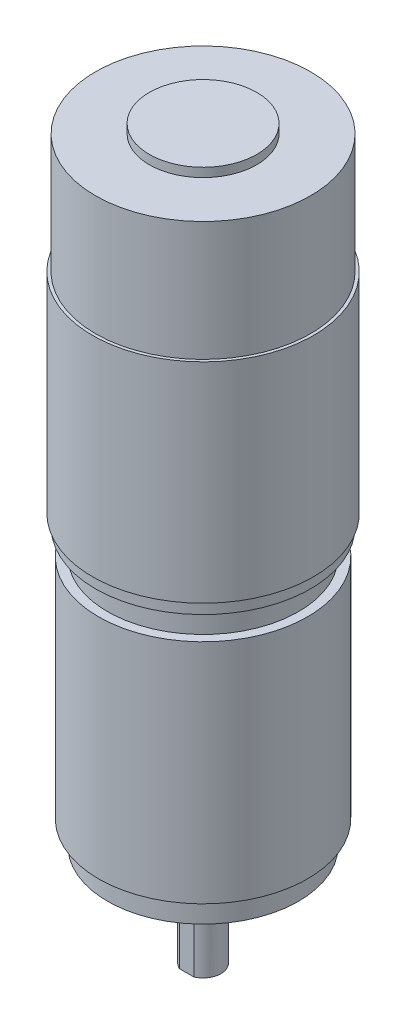
SolidWorks part; units mm, degrees
ref_plane "Спереди" through (0, 0, 0) normal (0, 0, 1) x (1, 0, 0)
ref_plane "Сверху" through (0, 0, 0) normal (0, 1, 0) x (1, 0, 0)
ref_plane "Справа" through (0, 0, 0) normal (1, 0, 0) x (0, 0, -1)
sketch "Эскиз1" plane through (0, 0, 0) normal (0, 0, 1) x (1, 0, 0)
  line L0 (0, -180.9093) -> (0, 224.9568) construction
  line L1 (0, 0) -> (-9, 0)
  line L2 (-9, 0) -> (-9, -1.5)
  line L3 (-9, -1.5) -> (-18, -1.5)
  line L4 (-18, -1.5) -> (-18, -21.5)
  line L5 (-18, -21.5) -> (-18.5, -21.5)
  line L6 (-18.5, -21.5) -> (-18.5, -56.5)
  line L7 (-18.5, -56.5) -> (-18, -56.5)
  line L8 (-18, -56.5) -> (-18, -58.5)
  line L9 (-18, -58.5) -> (-16, -58.5)
  line L10 (-16, -58.5) -> (-16, -62.8)
  line L11 (-16, -62.8) -> (-17.5, -62.8)
  line L12 (-17.5, -62.8) -> (-17.5, -100.8)
  line L13 (-17.5, -100.8) -> (-16, -100.8)
  line L14 (-16, -100.8) -> (-16, -104.8)
  line L15 (-16, -104.8) -> (-10, -104.8)
  line L16 (-10, -104.8) -> (-10, -106.8)
  line L17 (-10, -106.8) -> (-3, -106.8)
  line L20 (-3, -106.8) -> (-3, -121.8)
  line L21 (-3, -121.8) -> (0, -121.8)
  line L22 (0, 0) -> (0, -121.8)
  dimension "D3" = 10
  dimension "D4" = 16
  dimension "D6" = 15
  dimension "D7" = 17.5
  dimension "D8" = 16
  dimension "D9" = 18
  dimension "D10" = 18
  dimension "D11" = 18.5
  dimension "D12" = 20
  dimension "D13" = 2
  dimension "D14" = 4
  dimension "D15" = 38
  dimension "D17" = 2
  dimension "D18" = 35
  dimension "D19" = 9
  dimension "D20" = 1.5
  dimension "D21" = 4.3
  dimension "D22" = 1.5
  dimension "D23" = 3
revolve "Повернуть1" add sketch "Эскиз1" angle 360 about L0
sketch "Эскиз4" plane through (0, -121.8, 0) normal (0, -1, 0) x (1, 0, 0)
  line L1 (-3, 2.75) -> (3, 2.75)
  line L2 (-3, 2.75) -> (-3, -2.75)
  line L3 (-3, -2.75) -> (3, -2.75)
  line L4 (3, 2.75) -> (3, -2.75)
  line L5 (-3, 2.75) -> (3, -2.75) construction
  line L6 (-3, -2.75) -> (3, 2.75) construction
  circle A0 centre (0, 0) radius 3 construction
  circle A1 centre (0, 0) radius 3 construction
  point P0 (0, 0)
  dimension "D1" = 2.75
extrude "Вырез-Вытянуть2" cut sketch "Эскиз4" against normal blind 12 flip side to cut
sketch "Эскиз5" plane through (0, -104.8, 0) normal (0, -1, 0) x (1, 0, 0)
  line L4 (-9, 9) -> (9, 9) construction
  line L5 (-9, 9) -> (-9, -9) construction
  line L6 (-9, -9) -> (9, -9) construction
  line L7 (9, 9) -> (9, -9) construction
  line L8 (-9, 9) -> (9, -9) construction
  line L9 (-9, -9) -> (9, 9) construction
  circle A0 centre (-9, 9) radius 1.5
  circle A1 centre (9, 9) radius 1.5
  circle A2 centre (9, -9) radius 1.5
  circle A3 centre (-9, -9) radius 1.5
  point P8 (0, 0)
  point P15 (-9, -9)
  dimension "D1" = 3
  dimension "D2" = 3
  dimension "D3" = 3
  dimension "D4" = 3
  dimension "D6" = 18
  dimension "D9" = 18
extrude "Вырез-Вытянуть3" cut sketch "Эскиз5" against normal blind 5
